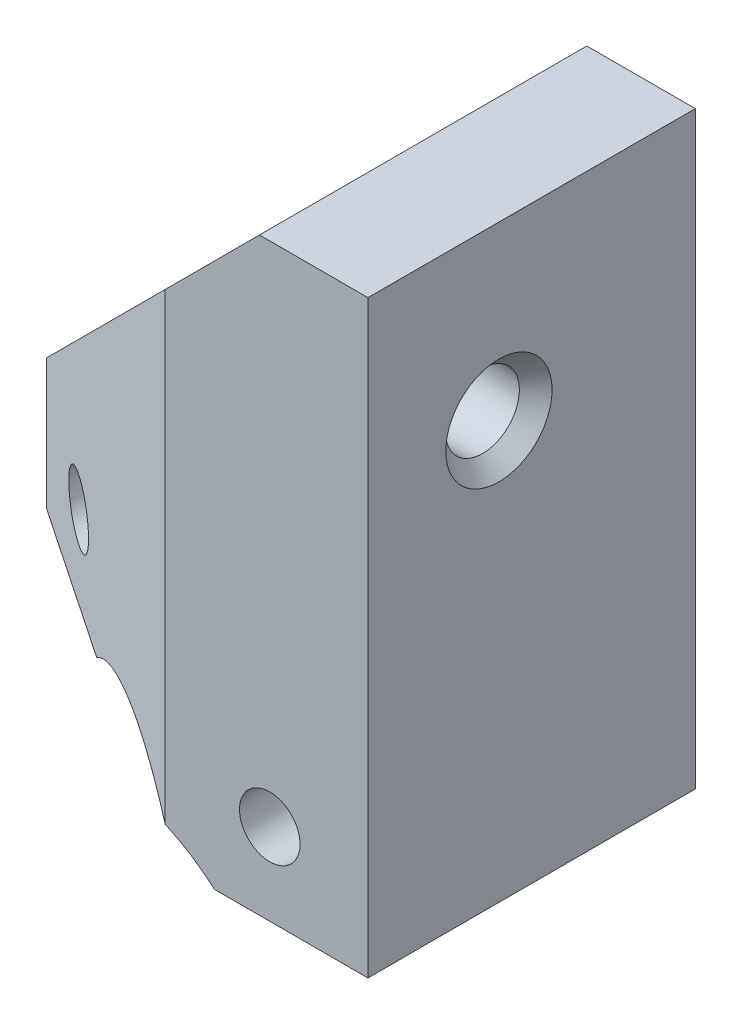
SolidWorks part; units mm, degrees
ref_plane "Front Plane" through (0, 0, 0) normal (0, 0, 1) x (1, 0, 0)
ref_plane "Top Plane" through (0, 0, 0) normal (0, 1, 0) x (1, 0, 0)
ref_plane "Right Plane" through (0, 0, 0) normal (1, 0, 0) x (0, 0, -1)
sketch "Sketch1" plane through (0, 0, 0) normal (0, 0, 1) x (1, 0, 0)
  line L0 (-11.315, 0) -> (11.315, 0) construction
  line L2 (-17.315, 5) -> (17.315, 5)
  line L3 (-17.315, 5) -> (-17.315, -5)
  line L4 (-17.315, -5) -> (17.315, -5)
  line L5 (17.315, 5) -> (17.315, -5)
  line L6 (-17.315, 5) -> (17.315, -5) construction
  line L7 (-17.315, -5) -> (17.315, 5) construction
  circle A0 centre (-11.315, 0) radius 1.85
  circle A1 centre (11.315, 0) radius 1.85
  point P4 (0, 0)
  point P7 (0, 0)
  dimension "D2" = 3.7
  dimension "D1" = 22.63
  dimension "D3" = 6
  dimension "D4" = 10
extrude "Boss-Extrude1" add sketch "Sketch1" along normal blind 20
chamfer "Chamfer1" distance 1 angle 45 2 edges at (-9.465, 0, 0) (13.165, 0, 0)
sketch "Sketch2" plane through (0, 0, 20) normal (0, 0, 1) x (1, 0, 0)
  line L0 (0, 0) -> (0, -14) construction
  circle A0 centre (0, -14) radius 12
  dimension "D1" = 24
  dimension "D2" = 14
extrude "Cut-Extrude1" cut sketch "Sketch2" against normal through all
sketch "Sketch3" plane through (0, 5, 0) normal (0, 1, 0) x (1, 0, 0)
  line L0 (-17.315, 0) -> (-17.315, -20)
  line L1 (-17.315, -20) -> (11.315, -20)
  line L2 (11.315, -20) -> (17.315, -20)
  line L3 (17.315, -20) -> (17.315, 0)
  line L4 (17.315, 0) -> (-17.315, 0)
  line L5 (17.315, -20) -> (17.315, 0) construction
  dimension "D1" = 6
  dimension "D2" = 20
extrude "Boss-Extrude2" add sketch "Sketch3" along normal blind 26
sketch "Sketch5" plane through (17.315, 0, 0) normal (1, 0, 0) x (0, 0, -1)
  line L0 (-20, 20.5) -> (-12, 20.5) construction
  line L1 (-20, 31) -> (-20, -5) construction
  line L2 (-20, 31) -> (0, 31) construction
  circle A0 centre (-12, 20.5) radius 2.25
  dimension "D2" = 4.5
  dimension "D1" = 10.5
  dimension "D3" = 8
extrude "Cut-Extrude3" cut sketch "Sketch5" against normal through all
chamfer "Chamfer2" distance 1 angle 45 1 edges at (17.315, 20.5, 9.75)
sketch "Sketch4" plane through (17.315, 0, 0) normal (1, 0, 0) x (0, 0, -1)
  line L1 (0, -5) -> (0, 31) construction
  line L2 (-12, 20.5) -> (0, 20.5) construction
  circle A0 centre (0, 20.5) radius 4
  circle A1 centre (0, 20.5) radius 8
  point P4 (0, 21.8334)
  dimension "D1" = 8
  dimension "D2" = 4
extrude "Cut-Extrude2" [suppressed] cut sketch "Sketch4" against normal blind 8 from offset 10 offset against normal yes
chamfer "Chamfer3" distance 28 angle 45 1 edges at (-17.315, 31, 10)
chamfer "Chamfer4" distance 15 angle 56 1 edges at (-17.315, -1, 20) first distance on face at (-17.315, -1, 10)
